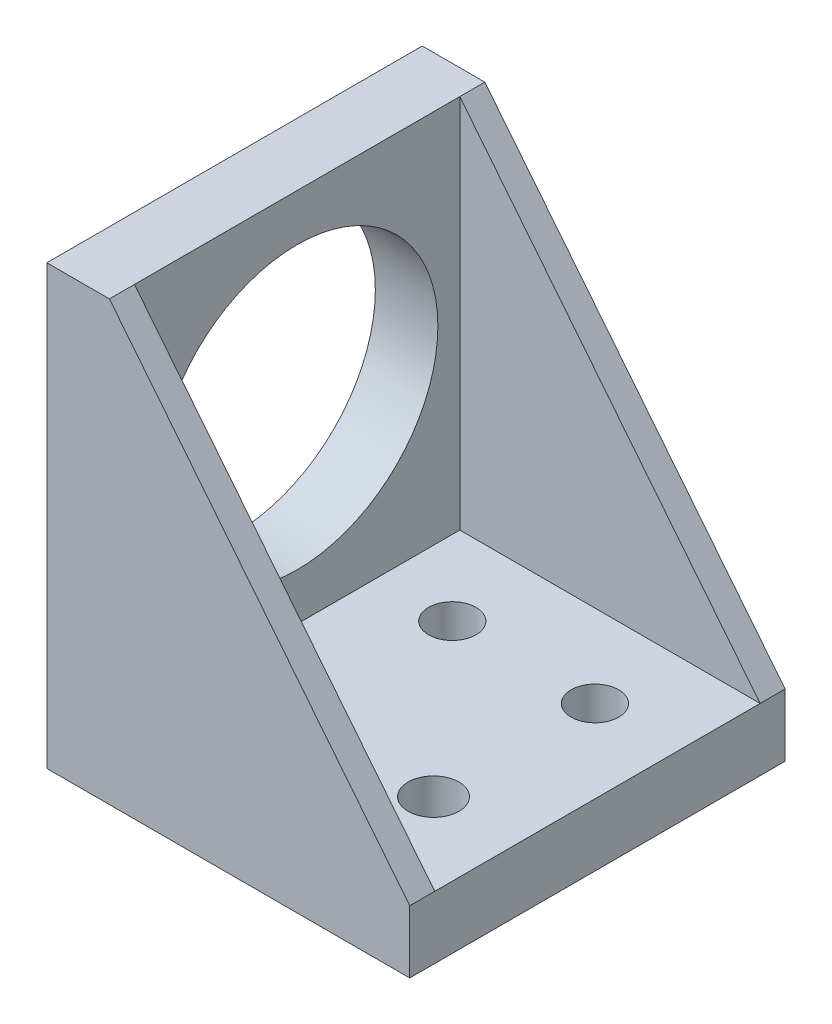
SolidWorks part; units mm, degrees
ref_plane "Front Plane" through (0, 0, 0) normal (0, 0, 1) x (1, 0, 0)
ref_plane "Top Plane" through (0, 0, 0) normal (0, 1, 0) x (1, 0, 0)
ref_plane "Right Plane" through (0, 0, 0) normal (1, 0, 0) x (0, 0, -1)
sketch "Sketch1" plane through (0, 0, 0) normal (1, 0, 0) x (0, 0, -1)
  line L5 (19.05, 19.05) -> (-19.05, 19.05)
  line L6 (19.05, 19.05) -> (19.05, -19.05)
  line L7 (19.05, -19.05) -> (-19.05, -19.05)
  line L8 (-19.05, 19.05) -> (-19.05, -19.05)
  line L9 (19.05, 19.05) -> (-19.05, -19.05) construction
  line L10 (19.05, -19.05) -> (-19.05, 19.05) construction
  line L11 (-19.05, -19.05) -> (19.05, -19.05)
  line L12 (-19.05, -19.05) -> (-19.05, -25.4)
  line L13 (-19.05, -25.4) -> (19.05, -25.4)
  line L14 (19.05, -19.05) -> (19.05, -25.4)
  circle A2 centre (0, 0) radius 14.2875
  dimension "D1" = 28.575
  dimension "D2" = 38.1
  dimension "D3" = 38.1
  dimension "D4" = 6.35
extrude "Boss-Extrude1" add sketch "Sketch1" along normal blind 30.48 contours L14 L7 L12 L13 region at (0, -22.225, 0)
extrude "Boss-Extrude2" add sketch "Sketch1<3>" against normal blind 6.35 separate body contours L5 L8 L7 L6 A2 region at (0, 0, -18.5112)
sketch "Sketch1<3>" plane through (0, 0, 0) normal (1, 0, 0) x (0, 0, -1) same geometry as "Sketch1"
sketch "Sketch3" plane through (0, -19.05, 0) normal (0, -1, 0) x (1, 0, 0)
  line L1 (-6.35, -19.05) -> (0, -19.05)
  line L2 (-6.35, -19.05) -> (-6.35, 19.05)
  line L3 (-6.35, 19.05) -> (0, 19.05)
  line L4 (0, -19.05) -> (0, 19.05)
extrude "Boss-Extrude3" add sketch "Sketch3" along normal blind 6.35 contours L2 L1 L4 L3
sketch "Sketch4" plane through (0, 0, 19.05) normal (0, 0, 1) x (1, 0, 0)
  line L0 (0, 19.05) -> (30.48, -19.05)
  line L1 (30.48, -19.05) -> (0, -19.05)
  line L2 (0, -19.05) -> (0, 19.05)
extrude "Boss-Extrude4" add sketch "Sketch4" against normal blind 2.54 contours L2 L0 L1
sketch "Sketch5" plane through (0, 0, -19.05) normal (0, 0, -1) x (-1, 0, 0)
  line L0 (0, 19.05) -> (-30.48, -19.05)
  line L1 (-30.48, -19.05) -> (0, -19.05)
  line L2 (0, -19.05) -> (0, 19.05)
extrude "Boss-Extrude5" add sketch "Sketch5" against normal blind 2.54
sketch "Sketch6" plane through (0, -19.05, 0) normal (0, 1, 0) x (1, 0, 0)
  line L2 (30.48, 16.51) -> (30.48, -16.51) construction
  line L3 (30.48, -16.51) -> (0, -16.51) construction
  line L4 (30.48, 16.51) -> (0, 16.51) construction
  circle A0 centre (7.62, 8.128) radius 2.413
  circle A1 centre (22.098, 8.128) radius 2.413
  circle A2 centre (7.62, -8.255) radius 2.413
  circle A3 centre (22.098, -8.255) radius 2.5797
  dimension "D1" = 4.826
  dimension "D2" = 4.826
  dimension "D3" = 4.826
  dimension "D4" = 5.1594
  dimension "D5" = 8.382
  dimension "D6" = 22.86
  dimension "D7" = 8.382
  dimension "D9" = 8.255
  dimension "D10" = 8.255
  dimension "D11" = 8.382
  dimension "D12" = 8.382
  dimension "D8" = 22.86
extrude "Cut-Extrude1" cut sketch "Sketch6" against normal through all contours A2 | A3 | A1 | A0 region at (7.62, -19.05, 8.255) region at (22.098, -19.05, 8.255)
